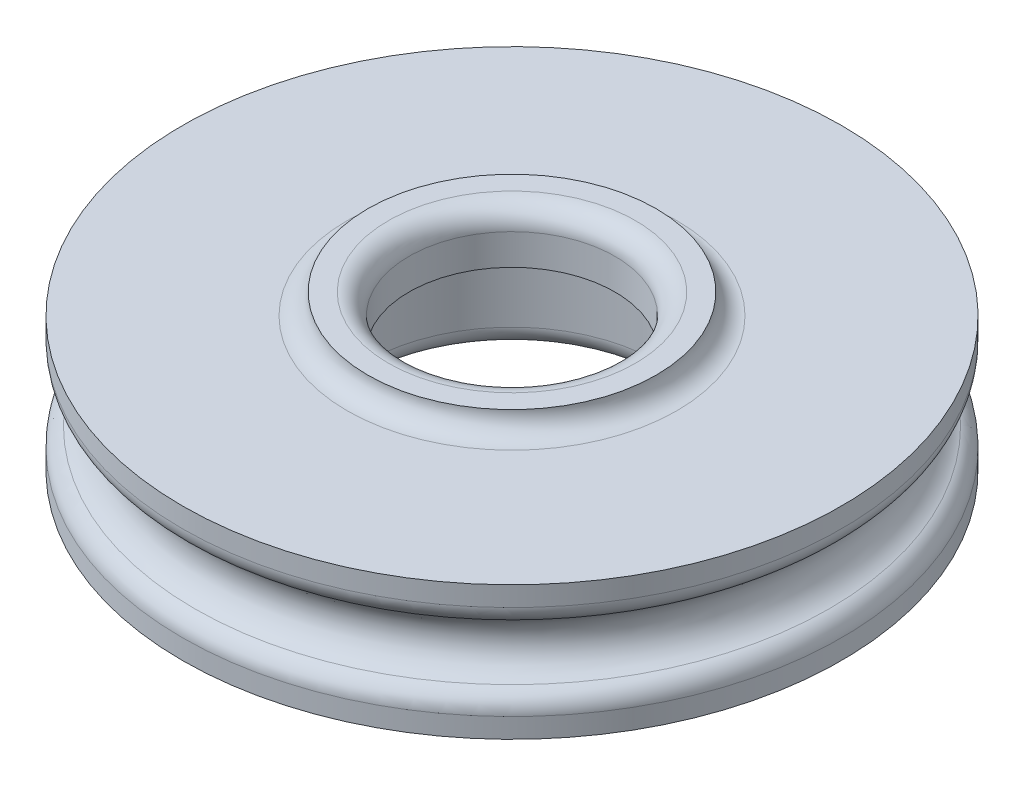
SolidWorks part; units mm, degrees
ref_plane "Front Plane" through (0, 0, 0) normal (0, 0, 1) x (1, 0, 0)
ref_plane "Top Plane" through (0, 0, 0) normal (0, 1, 0) x (1, 0, 0)
ref_plane "Right Plane" through (0, 0, 0) normal (1, 0, 0) x (0, 0, -1)
sketch "Sketch1" plane through (0, 0, 0) normal (0, 1, 0) x (1, 0, 0)
  circle A2 centre (0, 0) radius 3.55
  circle A3 centre (0, 0) radius 8
  dimension "D1" = 7.1
  dimension "D2" = 16
extrude "Boss-Extrude1" add sketch "Sketch1" along normal mid plane 3.25
sketch "Sketch2" plane through (0, 0, 0) normal (1, 0, 0) x (0, 0, -1)
  line L0 (-8, -1.625) -> (-8, -0.75) construction
  line L1 (-8, 1.625) -> (-8, -1.625) construction
  line L2 (-8, 1.625) -> (-8, 0.75) construction
  line L3 (-8, 0.75) -> (-8, -0.75)
  line L4 (-8, -1.625) -> (8, -1.625) construction
  line L5 (-8, 0) -> (-7.25, 0) construction
  ellipse E0 centre (-8, 0) end of major axis (-7.25, 0) minor radius 0.75 (-8, -0.75) -> (-8, 0.75) ccw
  dimension "D1" = 1.5
  dimension "D2" = 0.75
  dimension "D3" = 0.875
revolve "Cut-Revolve1" cut sketch "Sketch2" angle 360 about axis through (0, 1.625, 0) along (0, -1, 0)
sketch "Sketch3" plane through (0, 1.625, 0) normal (0, 1, 0) x (1, 0, 0)
  circle A0 centre (0, 0) radius 4
  circle A1 centre (0, 0) radius 2.5
  dimension "D1" = 5
  dimension "D2" = 8
extrude "Boss-Extrude2" add sketch "Sketch3" against normal blind 0.75
sketch "Sketch4" plane through (0, 1.625, 0) normal (0, 1, 0) x (1, 0, 0)
  circle A0 centre (0, 0) radius 2.5
  circle A1 centre (0, 0) radius 3.5
  dimension "D1" = 5
  dimension "D2" = 7
extrude "Boss-Extrude3" add sketch "Sketch4" along normal blind 0.5
fillet "Fillet2" radius 0.5 6 edges at (0, 0.875, 3.55) (0, -1.625, 3.55) (0, 1.625, 3.5) (0, 0.75, 8) (0, -0.75, 8) (0, 2.125, 2.5)
